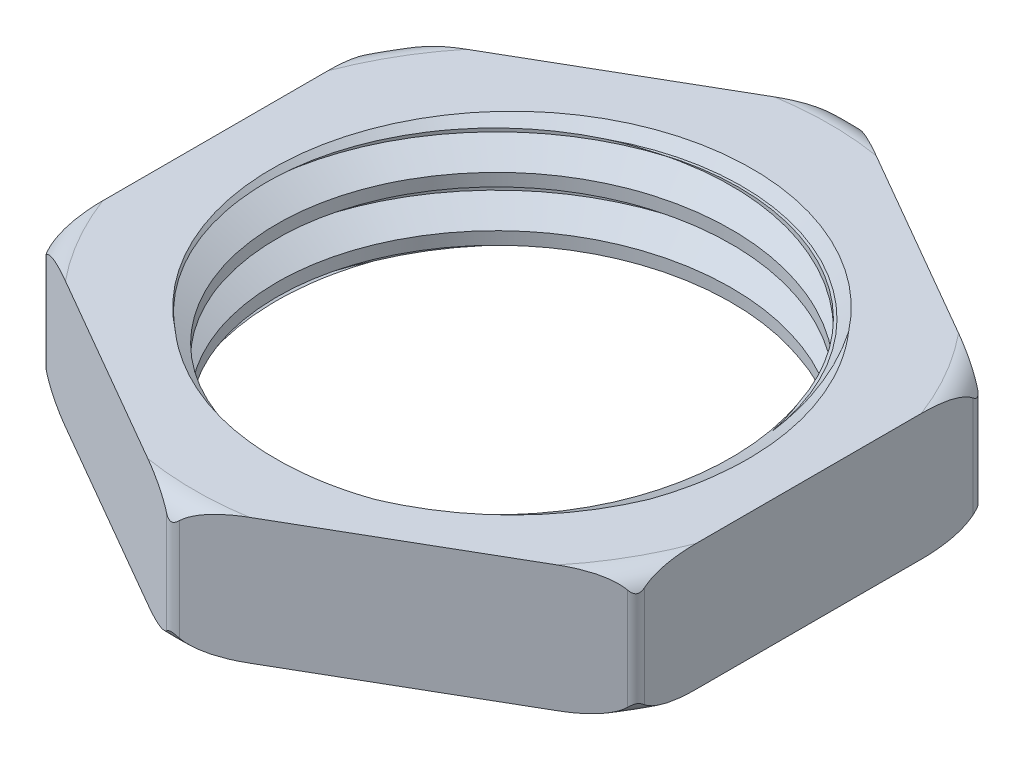
SolidWorks part; units mm, degrees
ref_plane "Front Plane" through (0, 0, 0) normal (0, 0, 1) x (1, 0, 0)
ref_plane "Top Plane" through (0, 0, 0) normal (0, 1, 0) x (1, 0, 0)
ref_plane "Right Plane" through (0, 0, 0) normal (1, 0, 0) x (0, 0, -1)
sketch "Sketch1" plane through (0, 0, 0) normal (0, 1, 0) x (1, 0, 0)
  line L1 (0, 6.7839) -> (-5.875, 3.3919)
  line L2 (-5.875, 3.3919) -> (-5.875, -3.3919)
  line L3 (-5.875, -3.3919) -> (0, -6.7839)
  line L4 (0, -6.7839) -> (5.875, -3.3919)
  line L5 (5.875, -3.3919) -> (5.875, 3.3919)
  line L6 (5.875, 3.3919) -> (0, 6.7839)
  circle A0 centre (0, 0) radius 5.875 construction
  dimension "D1" = 11.75
sketch "Sketch2" plane through (0, 0, 0) normal (0, 1, 0) x (1, 0, 0)
  circle A0 centre (0, 0) radius 6.7839
extrude "Boss-Extrude2" add sketch "Sketch2" along normal blind 3.5
sketch "Sketch3" plane through (0, 0, 0) normal (0, 1, 0) x (1, 0, 0)
  circle A0 centre (0, 0) radius 4.5
  dimension "D1" = 9
extrude "Cut-Extrude2" cut sketch "Sketch3" along normal up to next
thread "Thread1" pitch 1 start angle 0, offset 0, length 5, pitch 1, diameter 9
ref_plane "Plane2" through (-4.5, 3.5, 0) normal (0, 0, 1) x (-1, 0, 0)
sketch "Thread Profile2" plane through (-4.5, 3.5, 0) normal (0, 0, 1) x (-1, 0, 0)
  line L0 (0, 0) -> (0, 1) construction
  line L1 (0, 0) -> (0.5413, 0.3125)
  line L2 (0.5413, 0.3125) -> (0.5413, 0.4375)
  line L3 (0.5413, 0.4375) -> (0, 0.75)
  line L4 (0.5413, 0.375) -> (0, 0.375) construction
  line L11 (0, 0) -> (0, 0.75)
  point P2 (0, 0)
  dimension "Pitch" = 1
  dimension "Profile_Angle" = 60
  dimension "Profile_Land" = 0.125
  dimension "Profile_Height" = 0.5413
sketch "Sketch8" plane through (0, 0, 0) normal (0, 0, 1) x (1, 0, 0)
  line L5 (6.7839, 0) -> (6.7839, 3.5) construction
  line L6 (-6.7839, 3.5) -> (6.7839, 3.5)
  line L7 (-6.7839, 3.5) -> (-6.7839, 2.5)
  line L8 (-6.7839, 2.5) -> (6.7839, 2.5)
  line L9 (6.7839, 3.5) -> (6.7839, 2.5)
  line L10 (-6.7839, 0) -> (6.7839, 0) construction
  dimension "D1" = 2.5
extrude "Cut-Extrude3" cut sketch "Sketch8" against normal through all both and the other way through all
fillet "Fillet1" radius 0.5 2 edges at (0, 0, 6.7839) (0, 2.5, -6.7839)
extrude "Cut-Extrude1" cut sketch "Sketch1" along normal up to next (2.5 mm away) flip side to cut
fillet "Fillet2" radius 0.25 6 edges at (-5.875, 1.25, 3.3919) (-5.875, 1.25, -3.3919) (0, 1.25, -6.7839) (5.875, 1.25, -3.3919) (5.875, 1.25, 3.3919) (0, 1.25, 6.7839)
sketch "Sketch9" plane through (0, 0, 0) normal (0, 0, 1) x (1, 0, 0)
  line L0 (0, 0) -> (0, 3.4976) construction
  line L1 (-4.75, 2.5) -> (-4.55, 2.3)
  line L2 (-4.55, 2.3) -> (0, 2.3)
  line L3 (0, 2.3) -> (0, 2.5)
  line L4 (0, 2.5) -> (-4.75, 2.5)
  line L5 (1.9292, 2.5) -> (-4.5077, 2.5) construction
  line L8 (-5.875, 1.25) -> (5.875, 1.25) construction
  line L9 (-5.875, 2.2568) -> (-5.875, 0.2432) construction
  line L10 (5.875, 0.2432) -> (5.875, 2.2568) construction
  line L11 (0, 0) -> (-4.75, 0)
  line L12 (0, 0.2) -> (0, 0)
  line L13 (-4.55, 0.2) -> (0, 0.2)
  line L14 (-4.75, 0) -> (-4.55, 0.2)
  point P12 (-4.65, 2.4)
  dimension "D1" = 135
  dimension "D2" = 0.2
  dimension "D3" = 4.65
revolve "Cut-Revolve1" cut sketch "Sketch9" angle 360 about L0
